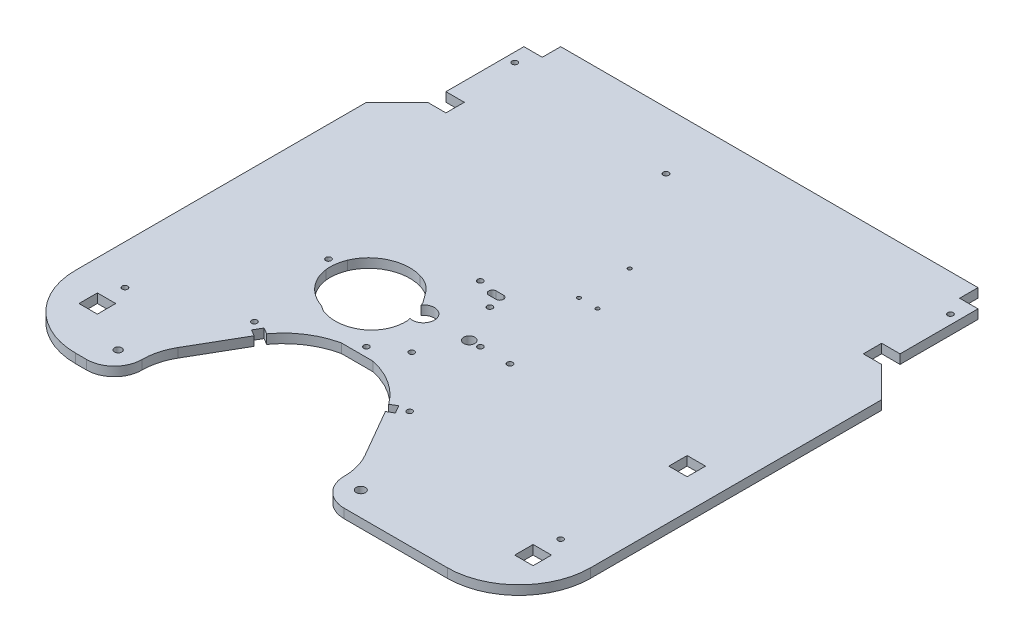
SolidWorks part; units mm, degrees
material "ABS PC"
ref_plane "Plan de face" through (0, 0, 0) normal (0, 0, 1) x (1, 0, 0)
ref_plane "Plan de dessus" through (0, 0, 0) normal (0, 1, 0) x (1, 0, 0)
ref_plane "Plan de droite" through (0, 0, 0) normal (1, 0, 0) x (0, 0, -1)
sketch "Esquisse1" plane through (0, 0, 0) normal (0, 1, 0) x (1, 0, 0)
  line L1 (-140.1, 31.2) -> (140.1, 31.2)
  line L2 (-140.1, 31.2) -> (-140.1, -245.0829)
  line L3 (-140.1, -245.0829) -> (140.1, -245.0829)
  line L4 (140.1, 31.2) -> (140.1, -245.0829)
  line L5 (45, -245.0829) -> (50, -245.0829) construction
  line L6 (-114.5, 31.2) -> (114.5, 31.2) construction
  line L7 (140.1, -4) -> (140.1, 4) construction
  line L8 (-140.1, 4) -> (-140.1, -4) construction
extrude "Boss.-Extru.1" add sketch "Esquisse1" along normal blind 5
sketch "Esquisse2" plane through (0, 0, 0) normal (0, 1, 0) x (1, 0, 0)
  line L3 (-58.1815, -184) -> (-61.6457, -182)
  line L4 (-61.6457, -182) -> (-64.1457, -186.3301)
  line L5 (-64.1457, -186.3301) -> (-60.6815, -188.3301)
  line L7 (-25, -132) -> (-25, -245.0829) construction
  line L8 (-58.1815, -184) -> (-60.6815, -188.3301) construction
  line L9 (-62.6323, -132) -> (62.6323, -132) construction
  line L10 (-25, -62.6323) -> (-25, 62.6323) construction
  line L11 (-60.6815, -188.3301) -> (-75.8539, -214.6094)
  line L13 (-58.1815, -184) -> (-54.7174, -186) construction
  line L14 (-25, -168.25) -> (-25, -231.25) construction
  line L16 (140.1, -245.0829) -> (-140.1, -245.0829) construction
  line L17 (-140.1, -245.0829) -> (140.1, -245.0829) construction
  line L18 (8.1815, -184) -> (4.7174, -186) construction
  line L20 (8.1815, -184) -> (10.6815, -188.3301) construction
  line L21 (10.6815, -188.3301) -> (25.8539, -214.6094)
  line L22 (14.1457, -186.3301) -> (10.6815, -188.3301)
  line L23 (11.6457, -182) -> (14.1457, -186.3301)
  line L24 (8.1815, -184) -> (11.6457, -182)
  line L25 (-62.8957, -184.1651) -> (-67.2258, -181.6651) construction
  line L26 (-95, -245.0829) -> (45, -245.0829)
  arc A0 (-95, -245.0829) -> (-86.2863, -217.8734) centre (-95, -230.0829) ccw construction
  arc A1 (8.1815, -184) -> (-58.1815, -184) centre (-25, -208.0829) ccw
  arc A2 (-95, -245.0829) -> (-80, -230.0829) centre (-95, -230.0829) ccw
  arc A4 (-80, -230.0829) -> (-75.8539, -214.6094) centre (-49.0531, -230.0829) cw
  arc A5 (30, -230.0829) -> (25.8539, -214.6094) centre (-0.9469, -230.0829) ccw
  arc A6 (45, -245.0829) -> (30, -230.0829) centre (45, -230.0829) cw
  circle A8 centre (-67.2258, -181.6651) radius 1.5
  circle A10 centre (17.2258, -181.6651) radius 1.5
  dimension "D4" = 41
  dimension "D8" = 5
  dimension "D9" = 3
  dimension "D1" = 4
  dimension "D2" = 52
  dimension "D3" = 37
  dimension "D5" = 90
  dimension "D6" = 5
  dimension "D7" = 30
extrude "Enlèv. mat.-Extru.2" cut sketch "Esquisse2" along normal through all
sketch "Esquisse3" plane through (0, 5, 0) normal (0, 1, 0) x (1, 0, 0)
  line L0 (-30.2198, -127.0596) -> (-26.1089, -139.1328)
  spline S0 degree 3 poles (-37.7914, -122.1402) (-38.0734, -121.8243) (-38.3657, -121.5165) (-38.9965, -120.9381) (-39.3221, -120.6716) (-39.9982, -120.1678) (-40.3476, -119.9323) (-41.0674, -119.4915) (-41.4393, -119.2855) (-41.8168, -119.0963) knots 0 0 0 0 0.25 0.25 0.5 0.5 0.75 0.75 1 1 1 1 construction
  spline S1 degree 3 poles (-32.1541, -129.7487) (-32.3725, -129.4202) (-32.6019, -129.0988) (-33.0628, -128.4574) (-33.2929, -128.1364) (-33.9829, -127.1734) (-34.442, -126.5306) (-35.3645, -125.2486) (-35.8282, -124.6096) (-36.7788, -123.3501) (-37.2654, -122.7294) (-37.7914, -122.1402) knots 0 0 0 0 0.125 0.125 0.25 0.25 0.5 0.5 0.75 0.75 1 1 1 1 construction
  spline S2 degree 3 poles (-35.6619, -154.1946) (-35.0242, -153.7971) (-34.4156, -153.3543) (-33.5487, -152.619) (-33.2665, -152.3609) (-32.7231, -151.8244) (-32.4631, -151.5476) (-31.717, -150.6924) (-31.2669, -150.0877) (-30.6603, -149.1305) (-30.4697, -148.8029) (-30.1129, -148.13) (-29.9465, -147.7839) (-29.4899, -146.7378) (-29.243, -146.0234) (-28.8562, -144.563) (-28.7157, -143.8147) (-28.4532, -141.5381) (-28.491, -140.0256) (-28.7111, -138.5175) knots 0 0 0 0 0.125 0.125 0.1875 0.1875 0.25 0.25 0.375 0.375 0.4375 0.4375 0.5 0.5 0.625 0.625 0.75 0.75 1 1 1 1 construction
  spline S3 degree 3 poles (-35.6619, -154.1946) (-36.3253, -154.608) (-37.0218, -154.968) (-38.4509, -155.5833) (-39.1871, -155.8402) (-40.6929, -156.2533) (-41.4552, -156.4075) (-42.998, -156.615) (-43.7804, -156.6676) (-46.0993, -156.6733) (-47.6259, -156.4799) (-49.5088, -155.9804) (-49.8836, -155.8673) (-50.622, -155.6166) (-50.9867, -155.4786) (-51.7066, -155.1765) (-52.0616, -155.0123) (-52.5826, -154.748) (-52.7564, -154.66) (-53.0886, -154.4564) (-53.2465, -154.3401) (-53.4028, -154.2206) knots 0 0 0 0 0.125 0.125 0.25 0.25 0.375 0.375 0.5 0.5 0.75 0.75 0.8125 0.8125 0.875 0.875 0.9375 0.9375 0.96875 0.96875 1 1 1 1 construction
  spline S4 degree 3 poles (-41.8168, -119.0963) (-42.9717, -118.5173) (-44.1778, -118.0898) (-46.0518, -117.6406) (-46.691, -117.5235) (-47.9689, -117.3572) (-48.6085, -117.3074) (-49.8889, -117.2725) (-50.5296, -117.2869) (-51.8124, -117.3808) (-52.4575, -117.4608) (-54.3583, -117.7944) (-55.5875, -118.1406) (-57.3737, -118.8468) (-57.9613, -119.1147) (-59.1074, -119.714) (-59.6598, -120.0407) (-61.253, -121.1053) (-62.2339, -121.9217) (-63.3433, -123.0959) (-63.5595, -123.3389) (-63.9727, -123.8343) (-64.1705, -124.0875) (-64.7392, -124.8624) (-65.0859, -125.3992) (-65.725, -126.5066) (-66.0166, -127.0778) (-66.4118, -127.9607) (-66.5364, -128.2602) (-66.7677, -128.8619) (-66.8752, -129.1647) (-67.3727, -130.6881) (-67.6417, -131.9376) (-67.7975, -133.5423) (-67.8198, -133.8663) (-67.8456, -134.511) (-67.8492, -134.8322) (-67.832, -135.7928) (-67.7828, -136.429) (-67.6138, -137.6932) (-67.494, -138.3213) (-67.1803, -139.5691) (-66.9857, -140.1898) (-66.3106, -141.9951) (-65.7352, -143.1386) (-64.7029, -144.7728) (-64.3296, -145.3033) (-63.5406, -146.3156) (-63.1238, -146.8009) (-62.2475, -147.7313) (-61.7884, -148.177) (-60.8134, -149.015) (-60.2997, -149.4102) (-59.6532, -149.8941) (-59.524, -149.9912) (-59.2621, -150.18) (-59.1281, -150.2696) (-58.7233, -150.5349) (-58.4482, -150.704) (-57.6091, -151.1904) (-57.0301, -151.4842) (-56.1848, -151.9623) (-55.907, -152.1283) (-55.4954, -152.386) (-55.361, -152.4765) (-55.1045, -152.6783) (-54.9822, -152.7884) (-54.7446, -153.015) (-54.6281, -153.1308) (-54.3929, -153.36) (-54.2744, -153.4736) (-53.9142, -153.8089) (-53.6638, -154.0209) (-53.4028, -154.2206) knots 0 0 0 0 0.0625 0.0625 0.09375 0.09375 0.125 0.125 0.15625 0.15625 0.1875 0.1875 0.25 0.25 0.28125 0.28125 0.3125 0.3125 0.375 0.375 0.390625 0.390625 0.40625 0.40625 0.4375 0.4375 0.46875 0.46875 0.484375 0.484375 0.5 0.5 0.5625 0.5625 0.578125 0.578125 0.59375 0.59375 0.625 0.625 0.65625 0.65625 0.6875 0.6875 0.75 0.75 0.78125 0.78125 0.8125 0.8125 0.84375 0.84375 0.875 0.875 0.882813 0.882813 0.890625 0.890625 0.90625 0.90625 0.9375 0.9375 0.953125 0.953125 0.960938 0.960938 0.96875 0.96875 0.976563 0.976563 0.984375 0.984375 1 1 1 1 construction
  spline S30 degree 3 poles (-26.1089, -139.1328) (-25.957, -141.5638) (-26.2233, -144.068) (-26.9566, -146.3908) knots 0 0 0 0 1 1 1 1
  spline S31 degree 3 poles (-26.9566, -146.3908) (-27.2228, -147.2342) (-27.8831, -148.8893) (-29.2029, -151.171) (-30.8763, -153.2749) (-32.1537, -154.4712) (-32.834, -155.0244) knots 0 0 0 0 0.25 0.5 0.75 1 1 1 1
  spline S32 degree 3 poles (-32.834, -155.0244) (-34.0816, -156.0391) (-36.8741, -157.7375) (-39.9456, -158.6891) (-41.5144, -158.9883) knots 0 0 0 0 0.5 1 1 1 1
  spline S33 degree 3 poles (-41.5144, -158.9883) (-44.1178, -159.4848) (-46.8613, -159.4832) (-49.4654, -158.9908) knots 0 0 0 0 1 1 1 1
  spline S34 degree 3 poles (-49.4654, -158.9908) (-49.952, -158.8988) (-50.9201, -158.6805) (-51.9843, -158.3611) (-52.6895, -158.1153) (-53.0279, -157.9903) (-53.4112, -157.8436) (-53.8185, -157.6386) (-54.1411, -157.4539) (-54.4726, -157.2537) (-54.8017, -157.0368) (-54.9983, -156.9002) (-55.0989, -156.8301) knots 0 0 0 0 0.25 0.5 0.5625 0.625 0.6875 0.75 0.8125 0.875 0.9375 1 1 1 1
  spline S35 degree 3 poles (-55.0989, -156.8301) (-55.3218, -156.6748) (-55.8004, -156.3308) (-56.3372, -156.039) (-57.1153, -155.7047) (-58.1073, -155.2831) (-59.4212, -154.7248) (-60.6952, -154.0815) (-61.7162, -153.4751) (-62.6513, -152.8651) (-64.3061, -151.7169) (-66.4424, -149.811) (-68.6708, -147.1371) (-71.0288, -143.199) (-72.0496, -139.8117) (-72.3207, -137.531) knots 0 0 0 0 0.03125 0.0625 0.09375 0.125 0.1875 0.25 0.28125 0.3125 0.375 0.5 0.625 0.75 1 1 1 1
  spline S36 degree 3 poles (-72.3207, -137.531) (-72.524, -135.8208) (-72.4832, -132.3293) (-71.5647, -128.9796) (-70.9127, -127.3896) knots 0 0 0 0 0.5 1 1 1 1
  spline S37 degree 3 poles (-70.9127, -127.3896) (-70.401, -126.1419) (-69.1411, -123.7476) (-66.5657, -120.5334) (-63.4815, -117.9312) (-59.9208, -115.9009) (-56.1194, -114.5638) (-52.0895, -113.8994) (-48.0382, -113.9466) (-45.3685, -114.4522) (-44.0724, -114.8246) knots 0 0 0 0 0.125 0.25 0.375 0.5 0.625 0.75 0.875 1 1 1 1
  spline S38 degree 3 poles (-44.0724, -114.8246) (-43.1335, -115.0943) (-41.3015, -115.7539) (-39.094, -116.9388) (-37.4723, -118.0859) (-36.3006, -119.1013) (-35.2972, -120.193) (-34.6853, -120.94) (-34.3845, -121.3211) knots 0 0 0 0 0.25 0.5 0.625 0.75 0.875 1 1 1 1
  spline S39 degree 3 poles (-34.3845, -121.3211) (-33.6538, -122.2469) (-32.5988, -123.6857) (-31.2416, -125.568) (-30.5443, -126.5566) (-30.2198, -127.0596) knots 0 0 0 0 0.5 0.75 1 1 1 1
  spline S40 degree 3 poles (-544.0684, -2053.4709) (-13.3203, -329.9447) (2.5957, -129.3013) (-46.0518, -117.6406) (-46.691, -117.5235) (-47.9689, -117.3572) (-48.6085, -117.3074) (-49.8889, -117.2725) (-50.5296, -117.2869) (-51.8124, -117.3808) (-52.4575, -117.4608) (-54.3583, -117.7944) (-55.5875, -118.1406) (-57.3737, -118.8468) (-57.9613, -119.1147) (-59.1074, -119.714) (-59.6598, -120.0407) (-61.253, -121.1053) (-62.2339, -121.9217) (-63.3433, -123.0959) (-63.5595, -123.3389) (-63.9727, -123.8343) (-64.1705, -124.0875) (-64.7392, -124.8624) (-65.0859, -125.3992) (-65.725, -126.5066) (-66.0166, -127.0778) (-66.4118, -127.9607) (-66.5364, -128.2602) (-66.7677, -128.8619) (-66.8752, -129.1647) (-67.3727, -130.6881) (-67.6417, -131.9376) (-67.7975, -133.5423) (-67.8198, -133.8663) (-67.8456, -134.511) (-67.8492, -134.8322) (-67.832, -135.7928) (-67.7828, -136.429) (-67.6138, -137.6932) (-67.494, -138.3213) (-67.1803, -139.5691) (-66.9857, -140.1898) (-66.3106, -141.9951) (-65.7352, -143.1386) (-64.7029, -144.7728) (-64.3296, -145.3033) (-63.5406, -146.3156) (-63.1238, -146.8009) (-62.2475, -147.7313) (-61.7884, -148.177) (-60.8134, -149.015) (-60.2997, -149.4102) (-59.6532, -149.8941) (-59.524, -149.9912) (-59.2621, -150.18) (-59.1281, -150.2696) (-58.7233, -150.5349) (-58.4482, -150.704) (-57.6091, -151.1904) (-57.0301, -151.4842) (-56.1848, -151.9623) (-55.907, -152.1283) (-55.4954, -152.386) (-55.361, -152.4765) (-55.1045, -152.6783) (-54.9822, -152.7884) (-54.7446, -153.015) (-54.6281, -153.1308) (-54.3929, -153.36) (-54.2744, -153.4736) (-26.8241, -179.0197) (131.7308, -54.8381) (1346.14, 1273.1767) knots -2.339844 -2.339844 -2.339844 -2.339844 0.0625 0.0625 0.09375 0.09375 0.125 0.125 0.15625 0.15625 0.1875 0.1875 0.25 0.25 0.28125 0.28125 0.3125 0.3125 0.375 0.375 0.390625 0.390625 0.40625 0.40625 0.4375 0.4375 0.46875 0.46875 0.484375 0.484375 0.5 0.5 0.5625 0.5625 0.578125 0.578125 0.59375 0.59375 0.625 0.625 0.65625 0.65625 0.6875 0.6875 0.75 0.75 0.78125 0.78125 0.8125 0.8125 0.84375 0.84375 0.875 0.875 0.882813 0.882813 0.890625 0.890625 0.90625 0.90625 0.9375 0.9375 0.953125 0.953125 0.960938 0.960938 0.96875 0.96875 0.976563 0.976563 0.984375 0.984375 2.762304 2.762304 2.762304 2.762304 only from (-41.8168, -119.0963) to (-53.4028, -154.2206)
  spline S41 degree 3 poles (-1939.2427, 445.2377) (-11.3915, 5.3531) (-2.0926, -139.9279) (-38.4509, -155.5833) (-39.1871, -155.8402) (-40.6929, -156.2533) (-41.4552, -156.4075) (-42.998, -156.615) (-43.7804, -156.6676) (-46.0993, -156.6733) (-47.6259, -156.4799) (-49.5088, -155.9804) (-49.8836, -155.8673) (-50.622, -155.6166) (-50.9867, -155.4786) (-51.7066, -155.1765) (-52.0616, -155.0123) (-52.5826, -154.748) (-52.7564, -154.66) (-62.008, -148.9921) (-46.7728, -99.7044) (-1052.7685, -1886.2862) knots -6.110057 -6.110057 -6.110057 -6.110057 0.125 0.125 0.25 0.25 0.375 0.375 0.5 0.5 0.75 0.75 0.8125 0.8125 0.875 0.875 0.9375 0.9375 0.96875 0.96875 2.678123 2.678123 2.678123 2.678123 only from (-35.6619, -154.1946) to (-53.4028, -154.2206)
  spline S42 degree 3 poles (805.3246, -1958.3687) (-625.9447, 427.7737) (-104.0787, -212.4384) (-33.5487, -152.619) (-33.2665, -152.3609) (-32.7231, -151.8244) (-32.4631, -151.5476) (-31.717, -150.6924) (-31.2669, -150.0877) (-30.6603, -149.1305) (-30.4697, -148.8029) (-30.1129, -148.13) (-29.9465, -147.7839) (-29.4899, -146.7378) (-29.243, -146.0234) (-28.8562, -144.563) (-28.7157, -143.8147) (-20.1781, -69.7717) (-507.9815, -8.4894) (1948.7508, 124.0064) knots -15.067184 -15.067184 -15.067184 -15.067184 0.125 0.125 0.1875 0.1875 0.25 0.25 0.375 0.375 0.4375 0.4375 0.5 0.5 0.625 0.625 0.75 0.75 12.82174 12.82174 12.82174 12.82174 only from (-35.6619, -154.1946) to (-28.7111, -138.5175)
  spline S43 degree 3 poles (-1678.0425, -1265.3241) (-10.5484, -165.9011) (-20.1896, -146.3733) (-33.0628, -128.4574) (-33.2929, -128.1364) (-33.9829, -127.1734) (-34.442, -126.5306) (-35.3645, -125.2486) (-35.8282, -124.6096) (-54.2717, -100.1715) (-88.436, -89.3419) (-1650.9877, -1303.2795) knots -6.732601 -6.732601 -6.732601 -6.732601 0.125 0.125 0.25 0.25 0.5 0.5 0.75 0.75 10.201277 10.201277 10.201277 10.201277 only from (-32.1541, -129.7487) to (-37.7914, -122.1402)
  spline S44 degree 3 poles (1561.6634, 1077.8271) (-67.121, -199.6011) (-22.5068, -136.058) (-38.9965, -120.9381) (-39.3221, -120.6716) (-39.9982, -120.1678) (-40.3476, -119.9323) (-65.1031, -104.7717) (-144.7605, -156.1255) (1752.928, -999.5442) knots -12.570471 -12.570471 -12.570471 -12.570471 0.25 0.25 0.5 0.5 0.75 0.75 17.69557 17.69557 17.69557 17.69557 only from (-37.7914, -122.1402) to (-41.8168, -119.0963)
extrude "Enlèv. mat.-Extru.3" cut sketch "Esquisse3" against normal through all
sketch "Esquisse4" plane through (0, 5, 0) normal (0, 1, 0) x (1, 0, 0)
  circle A0 centre (19.9, -82.15) radius 1
  circle A1 centre (9.8, -82.15) radius 1
  circle A2 centre (9.8, -54.55) radius 1
  dimension "D1" = 2
extrude "Enlèv. mat.-Extru.4" cut sketch "Esquisse4" against normal through all
sketch "Esquisse5" plane through (0, 5, 0) normal (0, 1, 0) x (1, 0, 0)
  circle A0 centre (22.1224, -132) radius 1.5
  circle A1 centre (-10.0508, -153.25) radius 1.5
  circle A2 centre (-25, -163) radius 1.5
  circle A3 centre (-10.0508, -110.75) radius 1.5
  circle A4 centre (-25, -101) radius 1.5
  circle A5 centre (-76.6, -132) radius 1.5
  circle A6 centre (6, -132) radius 1.5 construction
  circle A7 centre (6, -132) radius 1.5
  circle A8 centre (0, -132) radius 3
  arc A9 (1.5616, -134.5616) -> (1.5616, -129.4384) centre (0, -132) ccw construction
  circle A10 centre (-10.0508, -110.75) radius 1.5 construction
  dimension "D1" = 3
extrude "Enlèv. mat.-Extru.5" cut sketch "Esquisse5" against normal through all
sketch "Esquisse6" plane through (0, 5, 0) normal (0, 1, 0) x (1, 0, 0)
  circle A0 centre (-25, -132) radius 6
  circle A1 centre (-25, -132) radius 5.4 construction
  dimension "D1" = 12
extrude "Enlèv. mat.-Extru.6" cut sketch "Esquisse6" against normal through all
sketch "Esquisse7" plane through (0, 5, 0) normal (0, 1, 0) x (1, 0, 0)
  line L1 (-16, -103.4) -> (-12, -103.4) construction
  line L2 (-16, -101.4) -> (-12, -101.4)
  line L3 (-16, -105.4) -> (-12, -105.4)
  arc A0 (-16, -101.4) -> (-16, -105.4) centre (-16, -103.4) ccw
  arc A6 (-12, -105.4) -> (-12, -101.4) centre (-12, -103.4) ccw
  arc A7 (-11.4091, -103.2958) -> (-12.5909, -103.2958) centre (-12, -103.4) ccw construction
  arc A9 (-15.4091, -103.2958) -> (-16.5909, -103.2958) centre (-16, -103.4) ccw construction
  point P2 (-14, -103.4)
  dimension "D1" = 4
extrude "Enlèv. mat.-Extru.7" cut sketch "Esquisse7" against normal through all
sketch "Esquisse8" plane through (0, 5, 0) normal (0, 1, 0) x (1, 0, 0)
  line L0 (140.1, -245.0829) -> (140.1, 31.2) construction
  line L1 (101.1, -245.0829) -> (140.1, -245.0829)
  line L2 (140.1, -245.0829) -> (140.1, -206.0829)
  line L3 (-140.1, -245.0829) -> (-140.1, -206.0829)
  line L4 (-140.1, 31.2) -> (-140.1, -245.0829) construction
  line L5 (-140.1, -245.0829) -> (-95, -245.0829) construction
  line L6 (-101.1, -245.0829) -> (-140.1, -245.0829)
  arc A0 (140.1, -206.0829) -> (101.1, -245.0829) centre (101.1, -206.0829) cw
  arc A1 (-140.1, -206.0829) -> (-101.1, -245.0829) centre (-101.1, -206.0829) ccw
extrude "Enlèv. mat.-Extru.8" cut sketch "Esquisse8" against normal through all
sketch "Esquisse9" plane through (0, 5, 0) normal (0, 1, 0) x (1, 0, 0)
  line L0 (-113.5, 21.2) -> (-123.5, 21.2) construction
  line L1 (-113.5, 21.2) -> (-113.5, 31.2) construction
  line L2 (-113.5, -31.2) -> (-113.5, -21.2) construction
  line L3 (-113.5, -21.2) -> (-123.5, -21.2) construction
  line L4 (-113.5, -31.2) -> (-123.5, -31.2) construction
  line L5 (-113.5, 21.2) -> (-123.5, 21.2)
  line L6 (-113.5, 21.2) -> (-113.5, 31.2)
  line L7 (-113.5, -31.2) -> (-113.5, -21.2)
  line L8 (-113.5, -21.2) -> (-123.5, -21.2)
  line L9 (-113.5, -31.2) -> (-123.5, -31.2)
  line L10 (-123.5, -21.2) -> (-123.5, 21.2)
  line L11 (-123.5, -31.2) -> (-140.1, -47.8)
  line L12 (-140.1, 31.2) -> (-140.1, -206.0829) construction
  line L13 (-140.1, -47.8) -> (-140.1, 31.2)
  line L14 (-140.1, 31.2) -> (-113.5, 31.2)
  line L15 (0, 0) -> (0, 79.4635) construction
  line L16 (140.1, 31.2) -> (113.5, 31.2)
  line L17 (140.1, -47.8) -> (140.1, 31.2)
  line L18 (123.5, -31.2) -> (140.1, -47.8)
  line L19 (123.5, -21.2) -> (123.5, 21.2)
  line L20 (113.5, -31.2) -> (123.5, -31.2)
  line L21 (113.5, -21.2) -> (123.5, -21.2)
  line L22 (113.5, -31.2) -> (113.5, -21.2)
  line L23 (113.5, 21.2) -> (113.5, 31.2)
  line L24 (113.5, 21.2) -> (123.5, 21.2)
  dimension "D1" = 45
extrude "Enlèv. mat.-Extru.9" cut sketch "Esquisse9" against normal through all
sketch "Esquisse10" plane through (0, 0, 0) normal (0, -1, 0) x (1, 0, 0)
  line L1 (-100, 245.0829) -> (-100, 242.0829) construction
  line L2 (-95, 242.0829) -> (-100, 242.0829) construction
  line L4 (45, 242.0829) -> (50, 242.0829) construction
  line L5 (50, 242.0829) -> (50, 245.0829)
  line L6 (50, 245.0829) -> (45, 245.0829)
  line L7 (45, 242.0829) -> (50, 242.0829)
  line L8 (50, 245.0829) -> (50, 242.0829) construction
  line L9 (-101.1, 245.0829) -> (-95, 245.0829) construction
  line L11 (45, 245.0829) -> (50, 245.0829) construction
  line L20 (-95, 245.0829) -> (-100, 245.0829)
  line L21 (-100, 245.0829) -> (-100, 242.0829)
  line L22 (-100, 242.0829) -> (-95, 242.0829)
  arc A0 (-88.029, 220.3153) -> (-25, 23.5) centre (-25, 132) ccw construction
  arc A1 (-86.2863, 217.8734) -> (-25, 26.5) centre (-25, 132) ccw construction
  arc A2 (-25, 26.5) -> (36.2863, 217.8734) centre (-25, 132) ccw construction
  arc A3 (-25, 23.5) -> (38.029, 220.3153) centre (-25, 132) ccw construction
  arc A4 (-88.029, 220.3153) -> (-25, 23.5) centre (-25, 132) ccw
  arc A5 (-86.2863, 217.8734) -> (-25, 26.5) centre (-25, 132) ccw
  arc A6 (-25, 26.5) -> (36.2863, 217.8734) centre (-25, 132) ccw
  arc A7 (-25, 23.5) -> (38.029, 220.3153) centre (-25, 132) ccw
  arc A8 (45, 245.0829) -> (36.2863, 217.8734) centre (45, 230.0829) ccw construction
  arc A10 (45, 245.0829) -> (36.2863, 217.8734) centre (45, 230.0829) ccw
  arc A11 (45, 242.0829) -> (38.029, 220.3153) centre (45, 230.0829) ccw
  arc A12 (45, 242.0829) -> (38.029, 220.3153) centre (45, 230.0829) ccw construction
  arc A14 (-88.029, 220.3153) -> (-95, 242.0829) centre (-95, 230.0829) ccw construction
  arc A15 (-80, 230.0829) -> (-95, 245.0829) centre (-95, 230.0829) ccw construction
  arc A16 (-86.2863, 217.8734) -> (-95, 245.0829) centre (-95, 230.0829) ccw
  arc A17 (-88.029, 220.3153) -> (-95, 242.0829) centre (-95, 230.0829) ccw
extrude "Enlèv. mat.-Extru.10" [suppressed] cut sketch "Esquisse10" against normal blind 1
sketch "Esquisse11" plane through (0, 5, 0) normal (0, 1, 0) x (1, 0, 0)
  line L4 (-123.5, -210.8) -> (-123.5, -220.8)
  line L5 (-113.5, -210.8) -> (-123.5, -210.8)
  line L6 (-113.5, -220.8) -> (-113.5, -210.8)
  line L7 (-123.5, -220.8) -> (-113.5, -220.8)
  line L8 (-123.5, -210.8) -> (-123.5, -220.8)
  line L9 (-113.5, -210.8) -> (-123.5, -210.8)
  line L10 (-113.5, -220.8) -> (-113.5, -210.8)
  line L11 (-123.5, -220.8) -> (-113.5, -220.8)
  line L12 (113.5, -210.8) -> (113.5, -220.8)
  line L13 (123.5, -210.8) -> (113.5, -210.8)
  line L14 (123.5, -220.8) -> (123.5, -210.8)
  line L15 (113.5, -220.8) -> (123.5, -220.8)
  line L16 (113.5, -210.8) -> (113.5, -220.8)
  line L17 (123.5, -210.8) -> (113.5, -210.8)
  line L18 (123.5, -220.8) -> (123.5, -210.8)
  line L19 (113.5, -220.8) -> (123.5, -220.8)
  line L20 (123.5, -137) -> (123.5, -127)
  line L21 (113.5, -137) -> (123.5, -137)
  line L22 (113.5, -127) -> (113.5, -137)
  line L23 (123.5, -127) -> (113.5, -127)
  line L24 (123.5, -137) -> (123.5, -127)
  line L25 (113.5, -137) -> (123.5, -137)
  line L26 (113.5, -127) -> (113.5, -137)
  line L27 (123.5, -127) -> (113.5, -127)
  dimension "D1" = 0
  dimension "D2" = 0
  dimension "D3" = 0
extrude "Enlèv. mat.-Extru.11" cut sketch "Esquisse11" against normal through all
sketch "Esquisse12" plane through (0, 5, 0) normal (0, 1, 0) x (1, 0, 0)
  circle A0 centre (41, -232) radius 2.5 construction
  circle A1 centre (41, -232) radius 2.5
  circle A2 centre (-91, -232) radius 2 construction
  circle A3 centre (-91, -232) radius 2
extrude "Enlèv. mat.-Extru.12" cut sketch "Esquisse12" against normal through all
sketch "Esquisse13" plane through (0, 5, 0) normal (0, 1, 0) x (1, 0, 0)
  circle A0 centre (-118.5, -200.8) radius 1.5
  circle A1 centre (-118.5, 11.2) radius 1.5
  circle A2 centre (-118.5, 11.2) radius 1.525 construction
  circle A3 centre (-118.5, -200.8) radius 1.525 construction
  circle A4 centre (118.5, 11.2) radius 1.5
  circle A5 centre (118.5, -200.8) radius 1.5
  circle A6 centre (118.5, -200.8) radius 1.25 construction
  circle A7 centre (-25, 0) radius 1.5
  circle A9 centre (-25, 0) radius 1.5 construction
  dimension "D1" = 3
extrude "Enlèv. mat.-Extru.15" cut sketch "Esquisse13" against normal through all
sketch "Esquisse14" plane through (0, 0, 0) normal (0, -1, 0) x (1, 0, 0)
  line L0 (-115.5, 168) -> (115.5, 168) construction
  line L1 (-33.6234, 168) -> (-16.3766, 168)
  line L2 (-33.6234, 168) -> (-33.6234, 166)
  line L3 (-33.6234, 166) -> (-16.3766, 166)
  line L4 (-16.3766, 168) -> (-16.3766, 166)
  arc A0 (-58.1815, 184) -> (8.1815, 184) centre (-25, 208.0829) ccw construction
  dimension "D1" = 17.2468
  dimension "D2" = 2
extrude "Boss.-Extru.2" add sketch "Esquisse14" against normal up to surface (5 mm away) up to face at (-25, 5, 1.5)
